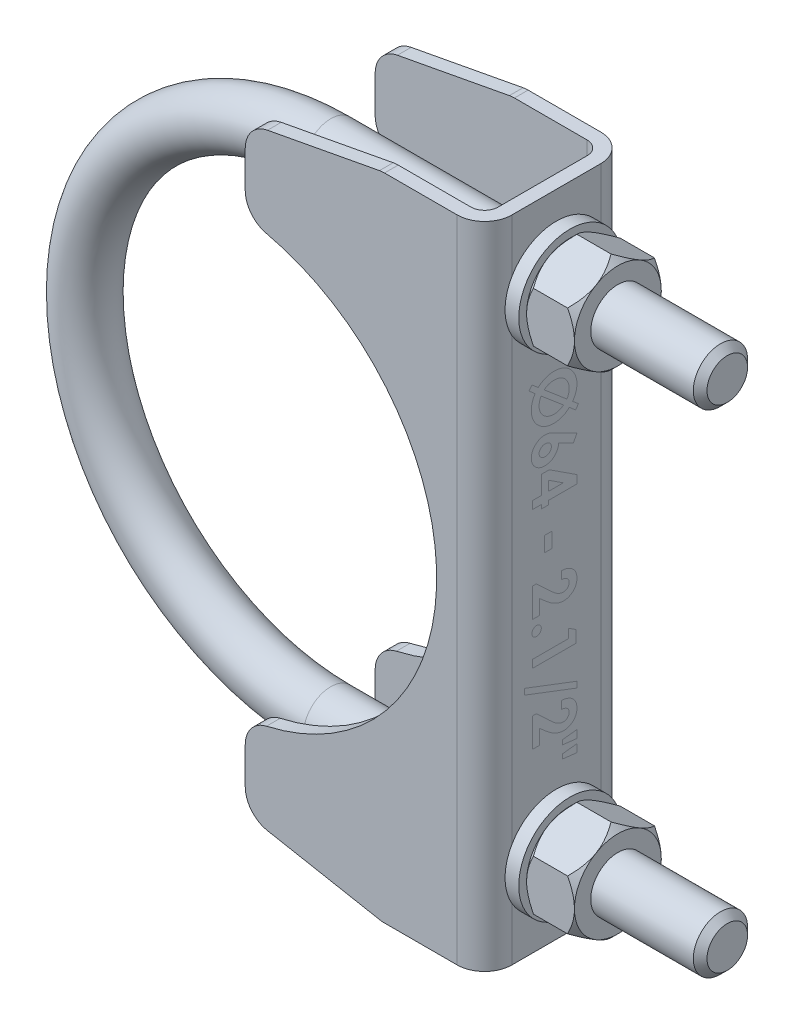
SolidWorks part; units mm, degrees
material "SAE 1045"
ref_plane "Front Plane" through (0, 0, 0) normal (0, 0, 1) x (1, 0, 0)
ref_plane "Top Plane" through (0, 0, 0) normal (0, 1, 0) x (1, 0, 0)
ref_plane "Right Plane" through (0, 0, 0) normal (1, 0, 0) x (0, 0, -1)
sketch "Esboço1" plane through (0, 0, 0) normal (0, 0, 1) x (1, 0, 0)
  line L0 (-58, 67.9688) -> (0, 67.9688) construction
  line L1 (-58, 3.9688) -> (0, 3.9688) construction
  line L2 (-58, 0) -> (0, 0)
  line L3 (-58, 71.9375) -> (0, 71.9375)
  line L4 (0, 71.9375) -> (0, 67.9688) construction
  line L5 (0, 0) -> (0, 3.9688) construction
  arc A0 (-58, 67.9688) -> (-58, 3.9688) centre (-58, 35.9688) ccw construction
  arc A1 (-58, 71.9375) -> (-58, 0) centre (-58, 35.9688) ccw
  arc A2 (-58, 67.9688) -> (-58, 3.9688) centre (-58, 35.9688) ccw construction
  dimension "D2" = 32
  dimension "D3" = 90
  dimension "D1" = 3.9688
sketch "Esboço2" plane through (0, 0, 0) normal (1, 0, 0) x (0, 0, -1)
  circle A0 centre (0, 0) radius 3.9688
sweep "Varredura1" add profiles "Esboço2" path "Esboço1"
cosmetic thread "Representação de rosca1" parameters "D1"=25, "D2"=6.2586
cosmetic thread "Representação de rosca2" parameters "D1"=25, "D2"=6.2586
chamfer "Chanfro1" distance 1 angle 45 2 edges at (0, 0, -3.9688) (0, 71.9375, -3.9688)
ref_plane "Plano1" through (-25, 0, 0) normal (1, 0, 0) x (0, 0, -1)
sketch "Esboço3" plane through (-25, 0, 0) normal (1, 0, 0) x (0, 0, -1)
  line L0 (0, 0) -> (0, 71.9375) construction
  line L1 (10.5, 83.4688) -> (-10.5, 83.4688)
  line L2 (10.5, 83.4688) -> (10.5, -11.5312)
  line L3 (10.5, -11.5312) -> (-10.5, -11.5312)
  line L4 (-10.5, 83.4688) -> (-10.5, -11.5312)
  line L5 (10.5, 83.4688) -> (-10.5, -11.5312) construction
  line L6 (10.5, -11.5312) -> (-10.5, 83.4688) construction
  line L7 (0, 73.6875) -> (0, 70.1875) construction
  line L8 (4.25, 73.6875) -> (4.25, 70.1875)
  line L9 (-4.25, 73.6875) -> (-4.25, 70.1875)
  line L10 (0, -1.75) -> (0, 1.75) construction
  line L11 (-4.25, -1.75) -> (-4.25, 1.75)
  line L12 (4.25, -1.75) -> (4.25, 1.75)
  arc A0 (4.25, 73.6875) -> (-4.25, 73.6875) centre (0, 73.6875) ccw
  arc A1 (-4.25, 70.1875) -> (4.25, 70.1875) centre (0, 70.1875) ccw
  arc A2 (-4.25, -1.75) -> (4.25, -1.75) centre (0, -1.75) ccw
  arc A3 (4.25, 1.75) -> (-4.25, 1.75) centre (0, 1.75) ccw
  point P0 (0, 35.9687)
  point P11 (0, 71.9375)
  point P17 (0, 0)
  dimension "D4" = 12
  dimension "D1" = 95
  dimension "D2" = 21
  dimension "D3" = 8.5
extrude "Ressalto-extrusão1" add sketch "Esboço3" against normal blind 2 separate body
sketch "Esboço4" plane through (0, 0, 10.5) normal (0, 0, 1) x (1, 0, 0)
  line L0 (-27, 83.4688) -> (-27, -11.5312) construction
  line L1 (-27, 83.4688) -> (-27, -11.5312)
  line L2 (-27, 83.4688) -> (-40, 83.4688)
  line L3 (-40, 83.4688) -> (-60, 79.7178)
  line L4 (-60, 79.7178) -> (-60, 67.7178)
  line L5 (-60, 4.2197) -> (-60, -7.7803)
  line L6 (-60, -7.7803) -> (-40, -11.5312)
  line L7 (-40, -11.5312) -> (-27, -11.5312)
  line L8 (-25, 83.4688) -> (-25, -11.5312) construction
  arc A0 (-60, 67.7178) -> (-60, 4.2197) centre (-64, 35.9687) cw
  dimension "D1" = 35
  dimension "D4" = 7
  dimension "D5" = 12
  dimension "D3" = 32
  dimension "D2" = 15
extrude "Ressalto-extrusão2" add sketch "Esboço4" against normal blind 2
mirror "Espelhar1" about plane through (0, 0, 0) normal (0, 0, 1) of "Ressalto-extrusão2"
fillet "Filete1" radius 2 2 edges at (-27, 35.9688, -8.5)
fillet "Filete2" radius 4 12 edges at (-60, 67.7178, -9.5) (-60, 79.7178, -9.5) (-60, 4.2197, -9.5) (-60, -7.7803, -9.5) (-60, -7.7803, 9.5) (-60, 4.2197, 9.5) (-60, 67.7178, 9.5) (-60, 79.7178, 9.5) (-40, 83.4688, 9.5) (-40, 83.4688, -9.5) (-25, 35.9688, -10.5) (-25, 35.9688, 10.5)
sketch "Esboço5" plane through (-25, 0, 0) normal (1, 0, 0) x (0, 0, -1)
  circle A0 centre (0, 71.9375) radius 7.5
  circle A1 centre (0, 0) radius 7.5
  circle A2 centre (0, 71.9375) radius 5
  circle A3 centre (0, 0) radius 5
  dimension "D1" = 15
  dimension "D2" = 10
extrude "Ressalto-extrusão3" add sketch "Esboço5" along normal blind 2
sketch "Esboço6" plane through (-23, 0, 0) normal (1, 0, 0) x (0, 0, -1)
  line L1 (-6.35, 75.6037) -> (-6.35, 68.2713)
  line L2 (-6.35, 68.2713) -> (0, 64.6052)
  line L3 (0, 64.6052) -> (6.35, 68.2713)
  line L4 (6.35, 68.2713) -> (6.35, 75.6037)
  line L5 (6.35, 75.6037) -> (0, 79.2698)
  line L6 (0, 79.2698) -> (-6.35, 75.6037)
  line L7 (6.35, 3.6662) -> (0, 7.3323)
  line L8 (0, 7.3323) -> (-6.35, 3.6662)
  line L9 (-6.35, 3.6662) -> (-6.35, -3.6662)
  line L10 (-6.35, -3.6662) -> (0, -7.3323)
  line L11 (0, -7.3323) -> (6.35, -3.6662)
  line L12 (6.35, -3.6662) -> (6.35, 3.6662)
  circle A0 centre (0, 71.9375) radius 6.35 construction
  circle A1 centre (0, 0) radius 6.35 construction
  dimension "D1" = 12.7
extrude "Ressalto-extrusão4" add sketch "Esboço6" along normal blind 7
sketch "Esboço7" plane through (0, 0, 0) normal (0, 0, 1) x (1, 0, 0)
  line L0 (-16, 78.2875) -> (-16, 79.2698)
  line L1 (-16, 79.2698) -> (-16, 75.6037) construction
  line L2 (-16, 79.2698) -> (-17, 79.2698)
  line L3 (-16, 79.2698) -> (-23, 79.2698) construction
  line L4 (-17, 79.2698) -> (-16, 78.2875)
  line L5 (0, 71.9375) -> (-31.8387, 71.9375) construction
  line L6 (0, 68.9688) -> (0, 74.9062) construction
  line L7 (-19.5, 79.2698) -> (-19.5, 85.6682) construction
  line L8 (-23, 78.2875) -> (-23, 79.2698)
  line L9 (-23, 79.2698) -> (-22, 79.2698)
  line L10 (-22, 79.2698) -> (-23, 78.2875)
  dimension "D1" = 12.7
  dimension "D2" = 1
revolve "Corte-Revolução1" cut sketch "Esboço7" angle 360 about L5
sketch "Esboço8" plane through (0, 0, 0) normal (0, 0, 1) x (1, 0, 0)
  line L0 (-16, 7.3323) -> (-17, 7.3323)
  line L1 (-16, 7.3323) -> (-23, 7.3323) construction
  line L2 (-17, 7.3323) -> (-16, 6.35)
  line L3 (-16, 7.3323) -> (-16, 3.6662) construction
  line L4 (-16, 6.35) -> (-16, 7.3323)
  line L5 (0, 0) -> (-19.7084, 0) construction
  line L6 (0, -2.9688) -> (0, 2.9688) construction
  line L7 (-19.5, 7.3323) -> (-19.5, 11.7477) construction
  line L8 (-23, 6.35) -> (-23, 7.3323)
  line L9 (-23, 7.3323) -> (-22, 7.3323)
  line L10 (-22, 7.3323) -> (-23, 6.35)
  dimension "D1" = 12.7
  dimension "D2" = 1
revolve "Corte-Revolução2" cut sketch "Esboço8" angle 360 about L5
sketch "Esboço9" plane through (-25, 0, 0) normal (1, 0, 0) x (0, 0, -1)
  line L0 (-3.5, 65.3043) -> (-3.5, 6.6332) construction
  line L1 (-10.5, -11.5312) -> (-10.5, 83.4688) construction
  arc A0 (6.5, 3.7417) -> (-6.5, 3.7417) centre (0, 0) ccw construction
  arc A1 (-6.5, 68.1958) -> (6.5, 68.1958) centre (0, 71.9375) ccw construction
  text T0 "Ø64 - 2.1/2\"" font "Century Gothic" height in points 24
  dimension "D1" = 7
wrap "Envolver1" sketch "Esboço9" wrap type scribe source sketch "Esboço9" face at (-25, 35.9687, 0)
